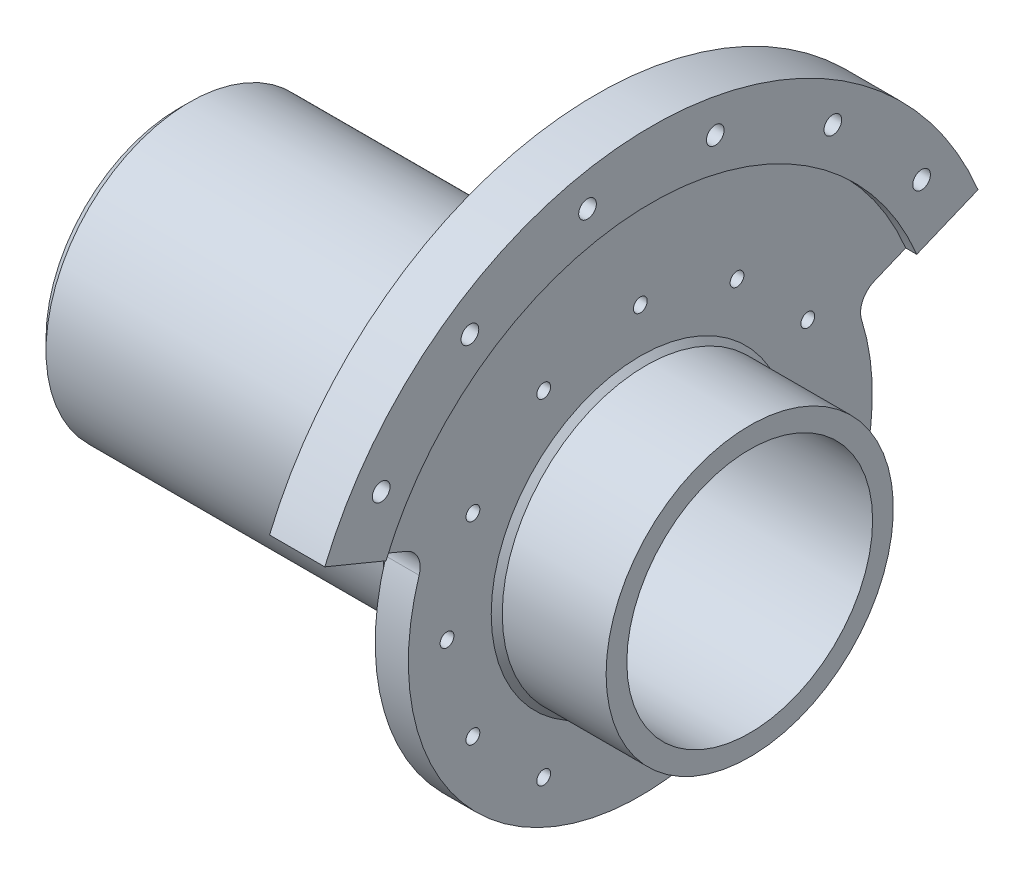
SolidWorks part; units mm, degrees
material "ABS"
ref_plane "Front Plane" through (0, 0, 0) normal (0, 0, 1) x (1, 0, 0)
ref_plane "Top Plane" through (0, 0, 0) normal (0, 1, 0) x (1, 0, 0)
ref_plane "Right Plane" through (0, 0, 0) normal (1, 0, 0) x (0, 0, -1)
sketch "Sketch1" plane through (0, 0, 0) normal (0, 0, 1) x (1, 0, 0)
  line L0 (0, 0) -> (61.0432, 0) construction
  line L1 (-40.3, 13) -> (11.4, 13)
  line L2 (-40.3, 13) -> (-40.3, 11.125)
  line L3 (-40.3, 11.125) -> (11.4, 11.125)
  line L4 (11.4, 13) -> (11.4, 11.125)
  dimension "D1" = 26
  dimension "D2" = 22.25
  dimension "D3" = 51.7
  dimension "D4" = 11.4
revolve "Revolve1" add sketch "Sketch1" angle 360 about L0
sketch "Sketch2" plane through (0, 0, 0) normal (0, 0, 1) x (1, 0, 0)
  line L0 (-40.3, 0) -> (10.8306, 0) construction
  line L1 (-40.3, 11.125) -> (-37.3, 11.125)
  line L2 (-40.3, 11.125) -> (-40.3, 7.5)
  line L3 (-40.3, 7.5) -> (-37.3, 7.5)
  line L4 (-37.3, 11.125) -> (-37.3, 7.5)
  line L5 (-40.3, 13) -> (-40.3, -13) construction
  dimension "D1" = 3
  dimension "D2" = 15
revolve "Revolve2" add sketch "Sketch2" angle 360 about L0
chamfer "Chamfer1" distance 1 angle 45 1 edges at (-40.3, 0, 13)
hole_wizard "M2 Clearance Hole1" positions "Sketch5" profile "Sketch4" hole size "M2" standard "DIN"
sketch "Sketch5" plane through (-40.3, 0, 0) normal (-1, 0, 0) x (0, 0, 1)
  circle A0 centre (0, 0) radius 9.5
  point P0 (0, 9.5)
  dimension "D1" = 19
sketch "Sketch4" plane through (-40.3, 9.5, 0) normal (0, 1, 0) x (0, 0, 1)
  line L0 (0, 0) -> (0, 11.5)
  line L1 (0, 11.5) -> (1.2, 11.5)
  line L2 (1.2, 11.5) -> (1.2, 0)
  line L5 (1.2, 0) -> (0, 0)
  line L10 (0, 11.5) -> (-1.2, 11.5) construction
  line L11 (0, -6.35) -> (0, 107.95) construction
  dimension "Hole Dia." = 2.4
  dimension "Hole Depth" = 11.5
  dimension "Drill Angle" = 180
pattern_circular "CirPattern1" count 6 over 360 about axis through (0, 0, 0) along (-1, 0, 0) of "M2 Clearance Hole1"
sketch "Sketch6" plane through (0, 0, 0) normal (0, 0, 1) x (1, 0, 0)
  line L0 (11.4, 13) -> (-39.3, 13) construction
  line L1 (1.5, 13) -> (-1.5, 13)
  line L2 (1.5, 13) -> (1.5, 32)
  line L3 (1.5, 32) -> (-1.5, 32)
  line L4 (-1.5, 13) -> (-1.5, 32)
  line L5 (1.5, 13) -> (-1.5, 32) construction
  line L6 (1.5, 32) -> (-1.5, 13) construction
  line L7 (0, 0) -> (16.7478, 0) construction
  point P0 (0, 22.5)
  dimension "D1" = 3
  dimension "D2" = 64
revolve "Revolve3" add sketch "Sketch6" angle 135 mid plane about L7
sketch "Sketch9" plane through (0, 0, 0) normal (0, 0, 1) x (1, 0, 0)
  line L1 (1.5, 21) -> (-1.5, 21)
  line L2 (1.5, 21) -> (1.5, 13)
  line L3 (1.5, 13) -> (-1.5, 13)
  line L4 (-1.5, 21) -> (-1.5, 13)
  line L6 (-1.5, 13) -> (-39.3, 13) construction
  line L8 (0, 0) -> (18.5465, 0) construction
  line L9 (0, 0) -> (0, 27.1673) construction
  dimension "D1" = 42
  dimension "D2" = 3
revolve "Revolve4" add sketch "Sketch9" angle 360 about L8
sketch "Sketch10" plane through (-1.5, 0, 0) normal (-1, 0, 0) x (0, 0, 1)
  line L0 (18.4662, 10) -> (55.6473, 5.965)
  line L1 (99.6548, 0) -> (0, 0) construction
  line L2 (18.4662, -10) -> (55.6473, -5.965)
  line L3 (18.4662, 10) -> (18.4662, -10) construction
  circle A0 centre (0, 0) radius 13.5
  arc A1 (18.4662, 10) -> (18.4662, -10) centre (0, 0) ccw
  circle A3 centre (0, 0) radius 13 construction
  circle A4 centre (39.5, 0) radius 3
  circle A5 centre (55, 0) radius 3
  arc A6 (55.6473, -5.965) -> (55.6473, 5.965) centre (55, 0) ccw
  dimension "D1" = 42
  dimension "D2" = 0.5
  dimension "D3" = 15.5
  dimension "D5" = 6
  dimension "D6" = 3
  dimension "D4" = 55
  dimension "D7" = 20
chamfer "Chamfer2" distance 0.5 angle 45 2 edges at (1.5, 0, 13) (-1.5, 0, 13)
sketch "Sketch11" plane through (0, 0, 0) normal (0, 0, 1) x (1, 0, 0)
  line L0 (0, 0) -> (20.6708, 0) construction
  line L1 (1.5, 32) -> (-3.5, 32)
  line L2 (1.5, 32) -> (1.5, 26)
  line L3 (1.5, 26) -> (-3.5, 26)
  line L4 (-3.5, 32) -> (-3.5, 26)
  dimension "D1" = 5
  dimension "D2" = 52
revolve "Revolve5" add sketch "Sketch11" angle 135 mid plane about L0
sketch "Sketch12" plane through (1.5, 0, 0) normal (1, 0, 0) x (0, 0, -1)
  point P0 (24.4584, 15.5817)
  point P1 (16.4258, 23.8997)
  point P2 (5.7817, 28.4178)
  point P3 (-5.7817, 28.4178)
  point P4 (-16.4258, 23.8997)
  point P5 (-24.4584, 15.5817)
chamfer "Chamfer4" distance 1 angle 45 1 edges at (-3.5, 32, 0)
hole_wizard "Tap Drill for M1.6 Tap1" positions "Sketch16" profile "Sketch15" hole size "M1.6" standard "DIN"
sketch "Sketch16" plane through (-1.5, 0, 0) normal (-1, 0, 0) x (0, 0, 1)
  circle A0 centre (0, 0) radius 17.5
  point P0 (0, 17.5)
  dimension "D1" = 35
sketch "Sketch15" plane through (-1.5, 17.5, 0) normal (0, 1, 0) x (0, 0, 1)
  line L0 (0, 0) -> (0, 11.5)
  line L1 (0, 11.5) -> (0.625, 11.5)
  line L2 (0.625, 11.5) -> (0.625, 0)
  line L5 (0.625, 0) -> (0, 0)
  line L10 (0, 11.5) -> (-0.625, 11.5) construction
  line L11 (0, -6.35) -> (0, 107.95) construction
  dimension "Hole Dia." = 1.25
  dimension "Hole Depth" = 11.5
  dimension "Drill Angle" = 180
pattern_circular "CirPattern2" count 12 over 360 about axis through (0, 0, 0) along (-1, 0, 0) of "Tap Drill for M1.6 Tap1"
fillet "Fillet1" radius 2 2 edges at (0, 8.0364, 19.4015) (0, 8.0364, -19.4015)
sketch "Sketch17" plane through (0, 0, 0) normal (0, 0, 1) x (1, 0, 0)
  line L0 (-2, 13) -> (-39.3, 13) construction
  line L1 (-4.3, 13) -> (-6.8, 13)
  line L2 (-4.3, 13) -> (-4.3, 14.95)
  line L3 (-4.3, 14.95) -> (-6.8, 14.95)
  line L4 (-6.8, 13) -> (-6.8, 14.95)
  line L5 (-40.3, 12) -> (-40.3, -12) construction
  line L6 (0, 0) -> (-56.4885, 0) construction
  dimension "D1" = 2.5
  dimension "D2" = 33.5
  dimension "D3" = 29.9
revolve "Revolve6" add sketch "Sketch17" angle 360 about L6
sketch "Esquisse1" plane through (0, 0, 0) normal (0, -0.9239, 0.3827) x (1, 0, 0)
  line L0 (-3.5, 31) -> (-2.5, 32)
  line L1 (-2.5, 32) -> (-3.5, 31) construction
  line L2 (-2.5, 32) -> (-2.5, 26)
  line L3 (-3.5, 26) -> (-1.5, 26) construction
  line L4 (-2.5, 26) -> (-3.5, 26)
  line L5 (-3.5, 26) -> (-3.5, 31)
  line L6 (-40.3, 0) -> (11.4, 0) construction
  line L7 (-40.3, 12) -> (-40.3, -12) construction
  line L8 (11.4, -13) -> (11.4, 13) construction
  dimension "D1" = 1
revolve "Enlèvement de matière-Révolution1" cut sketch "Esquisse1" angle 360 about L6
sketch "Esquisse2" plane through (0, 0, 0) normal (0, -0.9239, 0.3827) x (1, 0, 0)
  line L0 (1.5, 32) -> (2.5, 32)
  line L1 (2.5, 32) -> (2.5, 26)
  line L2 (2.5, 26) -> (1.5, 26)
  line L3 (1.5, 22.9129) -> (1.5, 32) construction
  line L4 (1.5, 26) -> (1.5, 32)
  line L5 (11.4, 0) -> (-40.3, 0) construction
  line L6 (11.4, -13) -> (11.4, 13) construction
  line L7 (-40.3, 12) -> (-40.3, -12) construction
  dimension "D1" = 1
revolve "Révolution4" add sketch "Esquisse2" angle 135 about L5
hole_wizard "Trou pour taraudage pour trou taraudé M21" positions "Sketch14" profile "Sketch13" hole size "M2" standard "DIN"
sketch "Sketch14" plane through (1.5, 0, 0) normal (1, 0, 0) x (0, 0, -1)
  point P0 (16.4258, 23.8997)
  point P1 (24.4584, 15.5817)
  point P3 (5.7817, 28.4178)
  point P5 (-5.7817, 28.4178)
  point P7 (-16.4258, 23.8997)
  point P9 (-24.4584, 15.5817)
sketch "Sketch13" plane through (1.5, 23.8997, -16.4258) normal (0, 1, 0) x (0, 0, -1)
  line L0 (0, -1) -> (0, 40.8)
  line L1 (0, 40.8) -> (0.8, 40.8)
  line L2 (0.8, 40.8) -> (0.8, -1)
  line L3 (-45.9899, -1) -> (13.1384, -1) construction
  line L5 (0.8, -1) -> (0, -1)
  line L10 (0, 40.8) -> (-0.8, 40.8) construction
  line L11 (0, -7.35) -> (0, 106.95) construction
  dimension "Diamètre du perçage" = 1.6
  dimension "Profondeur du perçage" = 41.8
  dimension "Angle de pointe" = 180
